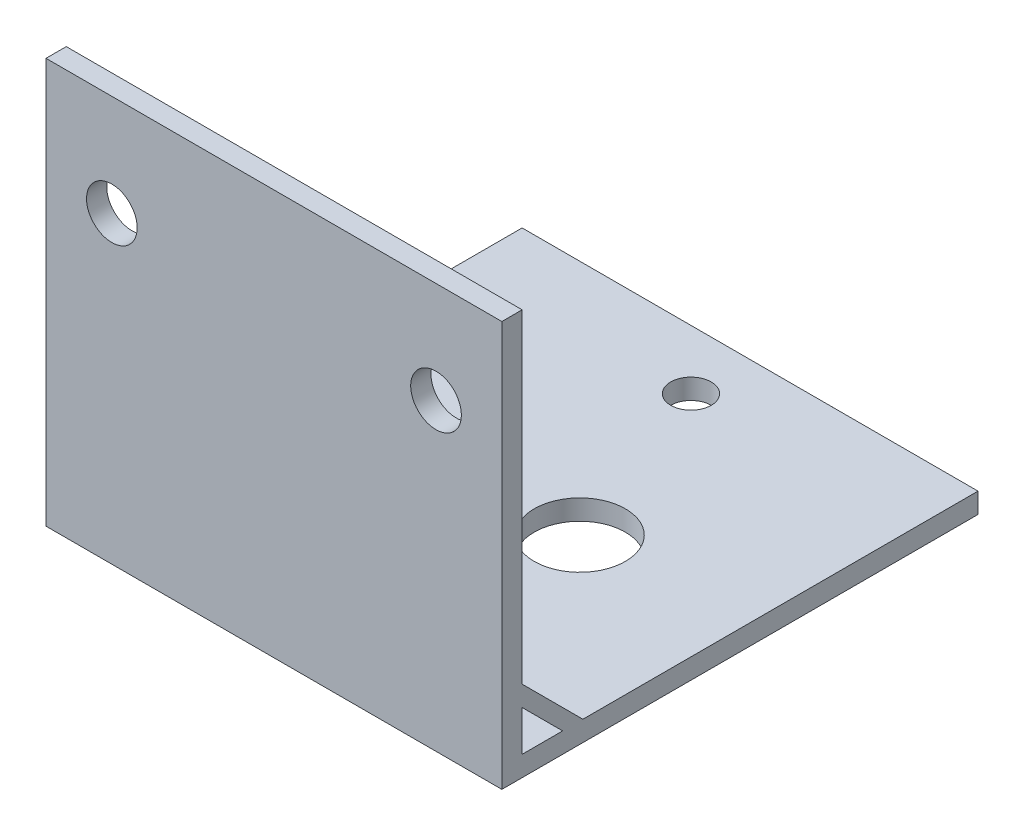
SolidWorks part; units mm, degrees
ref_plane "Front Plane" through (0, 0, 0) normal (0, 0, 1) x (1, 0, 0)
ref_plane "Top Plane" through (0, 0, 0) normal (0, 1, 0) x (1, 0, 0)
ref_plane "Right Plane" through (0, 0, 0) normal (1, 0, 0) x (0, 0, -1)
sketch "Sketch7" plane through (0, 0, 0) normal (0, 1, 0) x (1, 0, 0)
  line L0 (28.2563, -140.551) -> (-16.7437, -140.551)
  line L1 (28.2563, -95.551) -> (-16.7437, -95.551)
  line L2 (28.2563, -95.551) -> (28.2563, -142.551)
  line L3 (28.2563, -142.551) -> (-16.7437, -142.551)
  line L4 (-16.7437, -95.551) -> (-16.7437, -142.551)
  line L5 (28.2563, -95.551) -> (-16.7437, -142.551) construction
  line L6 (28.2563, -142.551) -> (-16.7437, -95.551) construction
  circle A0 centre (12.3619, -118.9637) radius 4.5
  circle A1 centre (5.362, -118.9853) radius 14
  circle A2 centre (5.7563, -101.3853) radius 2
  circle A3 centre (4.7594, -136.3853) radius 2
  circle A4 centre (12.3619, -118.9637) radius 3
  point P0 (5.7563, -119.051)
  point P7 (0, 0)
  point P17 (0, 0)
  point P18 (0, 0)
  dimension "D1" = 47
  dimension "D2" = 45
  dimension "D3" = 2
extrude "Boss-Extrude5" add sketch "Sketch7" along normal blind 2 separate body contours L1 L4 L0 L2 A3 A2 A1 | A1 A0 region at (5.7563, 0, 139.9146) region at (4.5555, 0, 118.9878)
extrude "Boss-Extrude6" add sketch "Sketch7<3>" along normal blind 40 contours L0 L4 L3 L2 region at (5.7563, 0, 141.551)
sketch "Sketch7<3>" plane through (0, 0, 0) normal (0, 1, 0) x (1, 0, 0) same geometry as "Sketch7"
sketch "Sketch8" plane through (-16.7437, 0, 0) normal (-1, 0, 0) x (0, 0, 1)
  line L0 (140.551, 6) -> (136.551, 2)
  line L1 (140.551, 40) -> (140.551, 2) construction
  line L2 (95.551, 2) -> (140.551, 2) construction
  line L3 (134.551, 2) -> (140.551, 8)
  line L4 (140.551, 8) -> (140.551, 6)
  line L5 (136.551, 2) -> (134.551, 2)
  dimension "D1" = 4
  dimension "D2" = 4
  dimension "D3" = 6
  dimension "D4" = 6
extrude "Boss-Extrude7" add sketch "Sketch8" against normal blind 2
ref_plane "Plane2" through (5.7563, 0, 0) normal (-1, 0, 0) x (0, 0, 1)
mirror "Mirror2" about plane through (5.7563, 0, 0) normal (-1, 0, 0) of "Boss-Extrude7"
sketch "Sketch9" plane through (0, 0, 142.551) normal (0, 0, 1) x (1, 0, 0)
  line L0 (5.7563, 22) -> (5.7563, -22) construction
  line L1 (-15.2437, 37) -> (26.7563, 37)
  line L2 (-15.2437, 37) -> (-15.2437, 23)
  line L3 (-15.2437, 23) -> (26.7563, 23)
  line L4 (26.7563, 37) -> (26.7563, 23)
  line L5 (-15.2437, 37) -> (26.7563, 23) construction
  line L6 (-15.2437, 23) -> (26.7563, 37) construction
  line L7 (28.2563, 0) -> (-16.7437, 0) construction
  point P0 (5.7563, 30)
  dimension "D1" = 23
  dimension "D2" = 14
  dimension "D3" = 42
sketch "Sketch10" plane through (0, 0, 142.551) normal (0, 0, 1) x (1, 0, 0)
  line L0 (26.7563, 37) -> (26.7563, 23) construction
  line L1 (-15.2437, 37) -> (26.7563, 37) construction
  line L2 (-15.2437, 37) -> (-15.2437, 23) construction
  circle A0 centre (21.7563, 30) radius 2.5
  circle A1 centre (-10.2437, 30) radius 2.5
  dimension "D1" = 5
  dimension "D2" = 5
  dimension "D4" = 5
  dimension "D3" = 7
  dimension "D5" = 7
  dimension "D6" = 5
extrude "Cut-Extrude2" cut sketch "Sketch10" against normal blind 2
